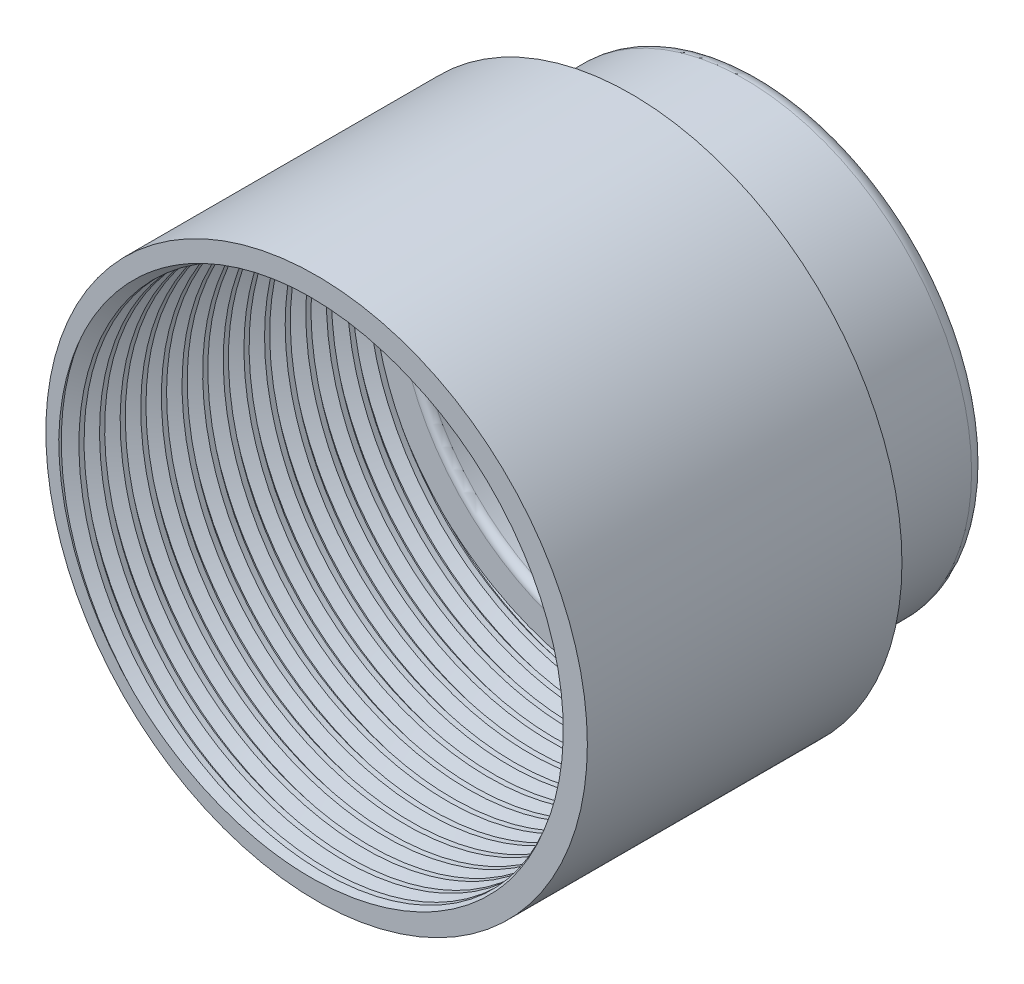
SolidWorks part; units mm, degrees
ref_plane "Plan de face" through (0, 0, 0) normal (0, 0, 1) x (1, 0, 0)
ref_plane "Plan de dessus" through (0, 0, 0) normal (0, 1, 0) x (1, 0, 0)
ref_plane "Plan de droite" through (0, 0, 0) normal (1, 0, 0) x (0, 0, -1)
sketch "Esquisse2" plane through (0, 0, 0) normal (0, 0, 1) x (1, 0, 0)
  circle A0 centre (-150, 595) radius 45 construction
  circle A1 centre (-150, 595) radius 45 construction
  circle A2 centre (-150, 595) radius 52.5
  circle A3 centre (-150, 595) radius 44
  circle A5 centre (-150, 595) radius 43
  circle A6 centre (-150, 595) radius 34
  circle A7 centre (-150, 595) radius 24
  circle A9 centre (-150, 595) radius 16.5
  circle A10 centre (-150, 595) radius 9
  circle A11 centre (-150, 595) radius 39
  circle A12 centre (-150, 595) radius 29
  circle A13 centre (-150, 595) radius 18.5
  circle A14 centre (-150, 595) radius 11
  circle M6 centre (-150, 595) radius 45
  dimension "D1" = 7.5
  dimension "D2" = 1
  dimension "D3" = 1
  dimension "D4" = 9
  dimension "D5" = 10
  dimension "D6" = 7.5
  dimension "D7" = 7.5
  dimension "D8" = 5
  dimension "D9" = 5
  dimension "D10" = 2
  dimension "D11" = 2
extrude "Boss.-Extru.1" add sketch "Esquisse2" along normal blind 1 contours A2 M6 | A3 M6 | A3 region at (-201.0151, 595, 0) region at (-193.8755, 595, 0) region at (-194.8727, 595, 0)
extrude "Boss.-Extru.2" add sketch "Esquisse2<3>" against normal blind 22 contours A3 A5 region at (-193.8755, 595, 0)
sketch "Esquisse2<3>" plane through (0, 0, 0) normal (0, 0, 1) x (1, 0, 0) same geometry as "Esquisse2"
extrude "Boss.-Extru.3" add sketch "Esquisse2<5>" against normal blind 3 from surface contours A3 | A6 starting at face at (-107, 595, -22)
sketch "Esquisse2<5>" plane through (0, 0, 0) normal (0, 0, 1) x (1, 0, 0) same geometry as "Esquisse2"
extrude "Boss.-Extru.4" add sketch "Esquisse2<6>" against normal blind 3 from surface contours A11 | A12 starting at face at (-116, 595, -25)
sketch "Esquisse2<6>" plane through (0, 0, 0) normal (0, 0, 1) x (1, 0, 0) same geometry as "Esquisse2"
extrude "Boss.-Extru.5" add sketch "Esquisse2<7>" against normal blind 3 from surface contours A6 | A7 starting at face at (-121, 595, -28)
sketch "Esquisse2<7>" plane through (0, 0, 0) normal (0, 0, 1) x (1, 0, 0) same geometry as "Esquisse2"
extrude "Boss.-Extru.6" add sketch "Esquisse2<8>" against normal blind 3 from surface contours A12 | A13 starting at face at (-126, 595, -31)
sketch "Esquisse2<8>" plane through (0, 0, 0) normal (0, 0, 1) x (1, 0, 0) same geometry as "Esquisse2"
extrude "Boss.-Extru.7" add sketch "Esquisse2<9>" against normal blind 3 from surface contours A7 | A9 starting at face at (-131.5, 595, -34)
sketch "Esquisse2<9>" plane through (0, 0, 0) normal (0, 0, 1) x (1, 0, 0) same geometry as "Esquisse2"
extrude "Boss.-Extru.8" add sketch "Esquisse2<10>" against normal blind 3 from surface separate body contours A13 starting at face at (-133.5, 595, -37)
sketch "Esquisse2<10>" plane through (0, 0, 0) normal (0, 0, 1) x (1, 0, 0) same geometry as "Esquisse2"
fillet "Congé1" radius 3 5 edges at (-126, 595, -37) (-121, 595, -34) (-116, 595, -31) (-111, 595, -28) (-106, 595, -25)
fillet "Congé2" radius 3 1 edges at (-131.5, 595, -40)
fillet "Congé3" radius 1.5 10 edges at (-133.5, 595, -34) (-131.5, 595, -31) (-126, 595, -28) (-121, 595, -25) (-116, 595, -22) (-107, 595, 1) (-126, 595, -31) (-121, 595, -28) (-116, 595, -25) (-107, 595, -22)
sketch "Esquisse3" plane through (0, 0, 1) normal (0, 0, 1) x (1, 0, 0)
  circle A0 centre (-150, 595) radius 52.5 construction
  circle A1 centre (-150, 595) radius 52.5
  circle A4 centre (-150, 595) radius 50
  dimension "D1" = 100
extrude "Boss.-Extru.9" add sketch "Esquisse3" along normal blind 60
thread "Filetage1" pitch 4 method extrude trim with start face yes trim with end face yes profile "Profil de filetage2" start angle 0, offset 3.5, length 63.5, pitch 4, diameter 100
ref_plane "Plan2" through (-200, 595, 64.5) normal (0, -1, 0) x (-1, 0, 0)
sketch "Profil de filetage2" plane through (-200, 595, 64.5) normal (0, -1, 0) x (-1, 0, 0)
  line L0 (0, 0) -> (0, 4) construction
  line L11 (0, 0) -> (0, 3.5)
  line L12 (0, 3.5) -> (-2.1651, 2.25)
  line L13 (-2.1651, 2.25) -> (-2.1651, 1.25)
  line L15 (-2.1651, 1.25) -> (0, 0)
  line L17 (-2.1651, 1.75) -> (0, 1.75) construction
  point P2 (0, 0)
  dimension "Pitch" = 4
  dimension "Profile_Angle" = 60
  dimension "Profile_Land" = 1
  dimension "Profile_Height" = 2.1651
scale "Echelle2" bodies to scale 112 110 scale about origin uniform scaling yes scale factor 0.5
